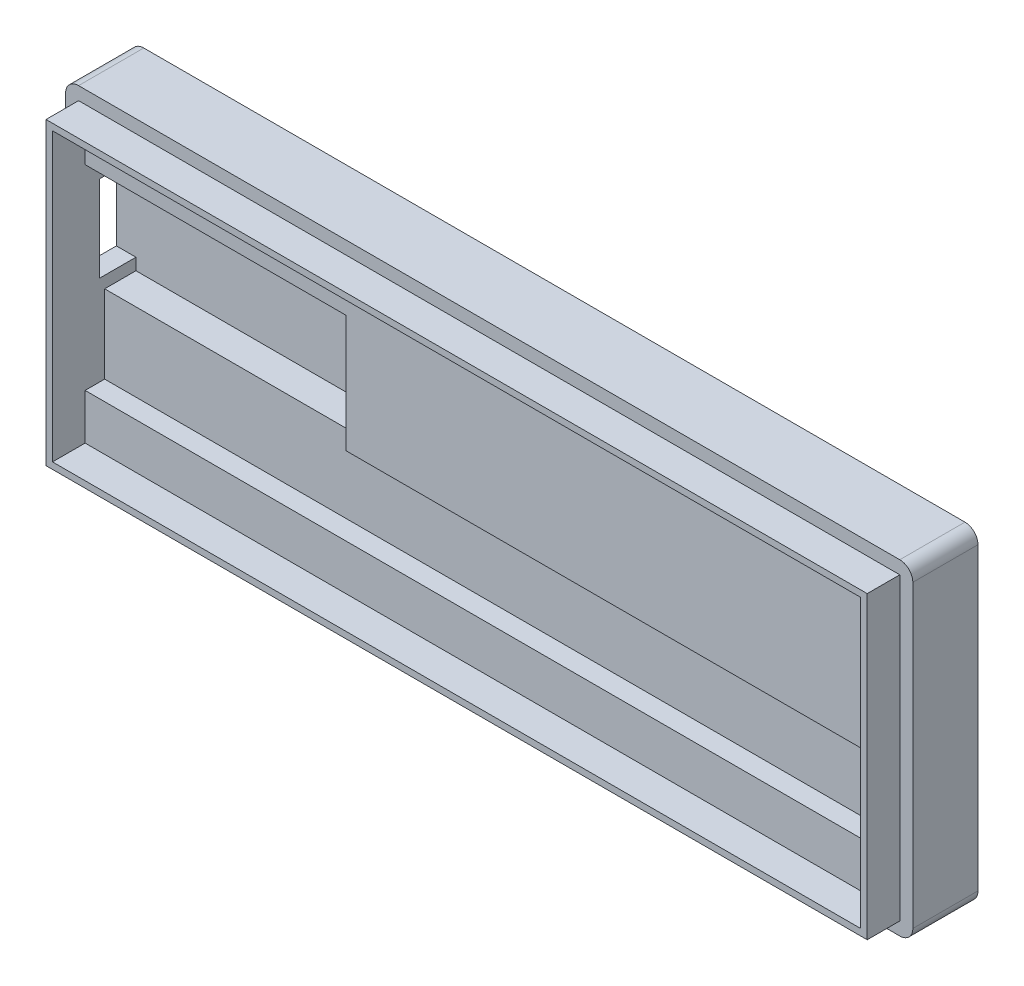
SolidWorks part; units mm, degrees
ref_plane "Přední rovina" through (0, 0, 0) normal (0, 0, 1) x (1, 0, 0)
ref_plane "Horní rovina" through (0, 0, 0) normal (0, 1, 0) x (1, 0, 0)
ref_plane "Pravá rovina" through (0, 0, 0) normal (1, 0, 0) x (0, 0, -1)
sketch "Skica2" plane through (0, 0, 0) normal (0, 0, 1) x (1, 0, 0)
  line L1 (-65.5, -25) -> (64.5, -25)
  line L2 (-65.5, -25) -> (-65.5, 25)
  line L3 (-65.5, 25) -> (64.5, 25)
  line L4 (64.5, -25) -> (64.5, 25)
  line L5 (-65.5, -25) -> (64.5, 25) construction
  line L6 (-65.5, 25) -> (64.5, -25) construction
  line L7 (-62.5, -3) -> (59.5, -3)
  line L8 (-62.5, -3) -> (-62.5, -15)
  line L9 (-62.5, -15) -> (59.5, -15)
  line L10 (59.5, -3) -> (59.5, -15)
  line L11 (-62.5, -3) -> (59.5, -15) construction
  line L12 (-62.5, -15) -> (59.5, -3) construction
  line L13 (-62.5, -3) -> (-22.5, -3)
  line L14 (-62.5, -3) -> (-62.5, 15)
  line L15 (-62.5, 15) -> (-22.5, 15)
  line L16 (-22.5, -3) -> (-22.5, 15)
  point P0 (0, 0)
  point P6 (-0.5, 0)
  point P13 (0, 0)
  point P14 (0, 0)
  dimension "D1" = 130
  dimension "D2" = 50
  dimension "D3" = 122
  dimension "D4" = 12
  dimension "D5" = 5
  dimension "D6" = 40
  dimension "D7" = 18
  dimension "D8" = 10
extrude "Přidat vysunutím1" add sketch "Skica2" against normal blind 10 contours L1 L4 L3 L2 L16 L7 L10 L9 L8 L14 L15 region at (6.8457, 2.0519, 0)
extrude "Přidat vysunutím3" add sketch "Skica2<7>" along normal blind 7 from surface contours L10 L7 L8 L9 region at (-1.5, -9, 0) starting at face at (-8.5, -1, -10)
sketch "Skica2<7>" plane through (0, 0, 0) normal (0, 0, 1) x (1, 0, 0) same geometry as "Skica2"
extrude "Přidat vysunutím4" add sketch "Skica2<8>" along normal blind 2.2 from surface contours L7 L16 L15 L14 region at (-42.5, 6, 0) starting at face at (-42.5, 6, -10)
sketch "Skica2<8>" plane through (0, 0, 0) normal (0, 0, 1) x (1, 0, 0) same geometry as "Skica2"
sketch "Skica3" plane through (-65.5, 0, 0) normal (-1, 0, 0) x (0, 0, 1)
  line L0 (-7.8, 12) -> (-2.2, -1.2) construction
  line L3 (-7.8, 12) -> (-2.2, 12)
  line L4 (-7.8, 12) -> (-7.8, -1.2)
  line L5 (-10, 25) -> (0, -25) construction
  line L6 (0, -25) -> (-10, -25) construction
  line L7 (-10, -25) -> (0, 25) construction
  line L8 (-7.8, -1.2) -> (-2.2, -1.2)
  line L9 (-2.2, 12) -> (-2.2, -1.2)
  line L11 (-10, 25) -> (0, 25) construction
  point P6 (-5, 0)
  point P9 (-5, 5.4)
  dimension "D1" = 13.2
  dimension "D2" = 5.6
  dimension "D4" = 13
extrude "Odebrat vysunutím12" cut sketch "Skica3" against normal blind 11
sketch "Skica4" plane through (0, 0, 0) normal (0, 0, 1) x (1, 0, 0)
  line L0 (-65.5, -25) -> (64.5, -25) construction
  line L1 (-63.5, 23) -> (62.5, 23)
  line L2 (-63.5, 23) -> (-63.5, -23)
  line L3 (-63.5, -23) -> (62.5, -23)
  line L4 (62.5, 23) -> (62.5, -23)
  line L5 (-65.5, 25) -> (64.5, 25) construction
  line L8 (-65.5, -25) -> (-65.5, 25) construction
  line L12 (-62.5, 22) -> (61.5, 22)
  line L13 (-62.5, 22) -> (-62.5, -22)
  line L14 (-62.5, -22) -> (61.5, -22)
  line L15 (61.5, 22) -> (61.5, -22)
  point P0 (0, 0)
  point P6 (0, 0)
  dimension "D1" = 126
  dimension "D2" = 2
  dimension "D3" = 124
  dimension "D4" = 1
  dimension "D5" = 2
  dimension "D6" = 2
  dimension "D7" = 44
  dimension "D8" = 1
extrude "Přidat vysunutím5" add sketch "Skica4" along normal blind 5
fillet "Zaoblit1" radius 2 4 edges at (-65.5, 25, -5) (64.5, 25, -5) (64.5, -25, -5) (-65.5, -25, -5)
